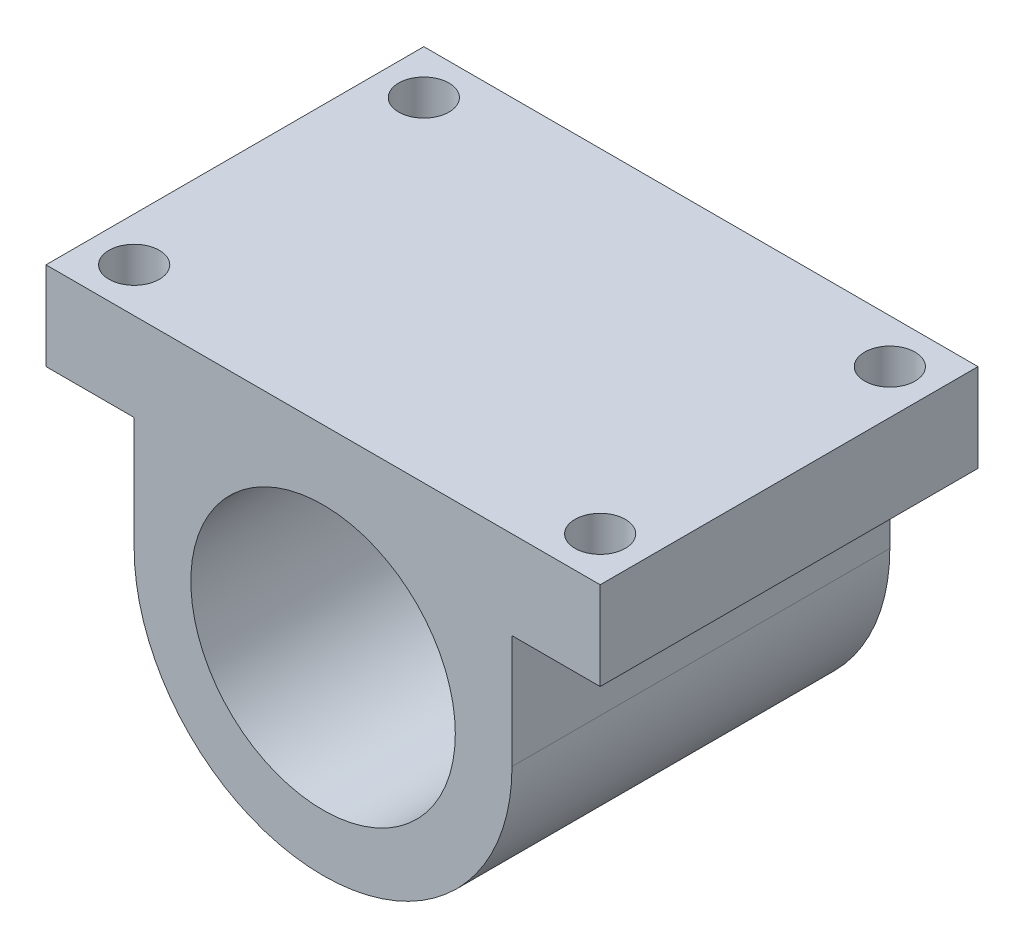
SolidWorks part; units mm, degrees
ref_plane "Спереди" through (0, 0, 0) normal (0, 0, 1) x (1, 0, 0)
ref_plane "Сверху" through (0, 0, 0) normal (0, 1, 0) x (1, 0, 0)
ref_plane "Справа" through (0, 0, 0) normal (1, 0, 0) x (0, 0, -1)
sketch "Эскиз1" plane through (0, 0, 0) normal (0, 0, 1) x (1, 0, 0)
  line L0 (0, 0) -> (0, 31) construction
  line L1 (-15, 0) -> (15, 0)
  line L2 (15, 0) -> (15, 31)
  line L3 (15, 31) -> (-15, 31)
  line L4 (-15, 31) -> (-15, 0)
  circle A0 centre (0, 15) radius 10.5
  dimension "D1" = 21
  dimension "D2" = 30
  dimension "D3" = 15
  dimension "D4" = 16
extrude "Бобышка-Вытянуть1" add sketch "Эскиз1" along normal blind 30
fillet "Скругление1" radius 15 1 edges at (15, 0, 15)
fillet "Скругление2" radius 15 1 edges at (-15, 0, 15)
sketch "Эскиз2" plane through (15, 0, 0) normal (1, 0, 0) x (0, 0, -1)
  line L0 (0, 31) -> (0, 24)
  line L1 (0, 15) -> (0, 31) construction
  line L2 (0, 24) -> (-30, 24)
  line L3 (-30, 15) -> (-30, 31) construction
  line L4 (-30, 24) -> (-30, 31)
  line L5 (-30, 31) -> (0, 31)
  dimension "D1" = 7
extrude "Бобышка-Вытянуть2" add sketch "Эскиз2" along normal blind 7
sketch "Эскиз3" plane through (-15, 0, 0) normal (-1, 0, 0) x (0, 0, 1)
  line L0 (30, 31) -> (0, 31)
  line L1 (0, 31) -> (0, 24)
  line L2 (0, 31) -> (0, 15) construction
  line L3 (0, 24) -> (30, 24)
  line L4 (30, 31) -> (30, 15) construction
  line L5 (30, 24) -> (30, 31)
  dimension "D1" = 7
extrude "Бобышка-Вытянуть3" add sketch "Эскиз3" along normal blind 7
sketch "Эскиз4" plane through (0, 31, 0) normal (0, 1, 0) x (1, 0, 0)
  line L0 (-22, -30) -> (-22, 0) construction
  line L1 (22, 0) -> (-22, 0) construction
  line L2 (0, 0) -> (0, -30) construction
  line L3 (22, -30) -> (-22, -30) construction
  line L4 (-22, -15) -> (22, -15) construction
  line L5 (22, 0) -> (22, -30) construction
  circle A0 centre (18.5, -3.5) radius 2
  circle A1 centre (18.5, -26.5) radius 2
  circle A2 centre (-18.5, -26.5) radius 2
  circle A3 centre (-18.5, -3.5) radius 2
  dimension "D1" = 4
  dimension "D2" = 3.5
  dimension "D3" = 3.5
extrude "Вырез-Вытянуть1" cut sketch "Эскиз4" against normal up to surface (7 mm away) up to face at (18.5, 24, 15)
